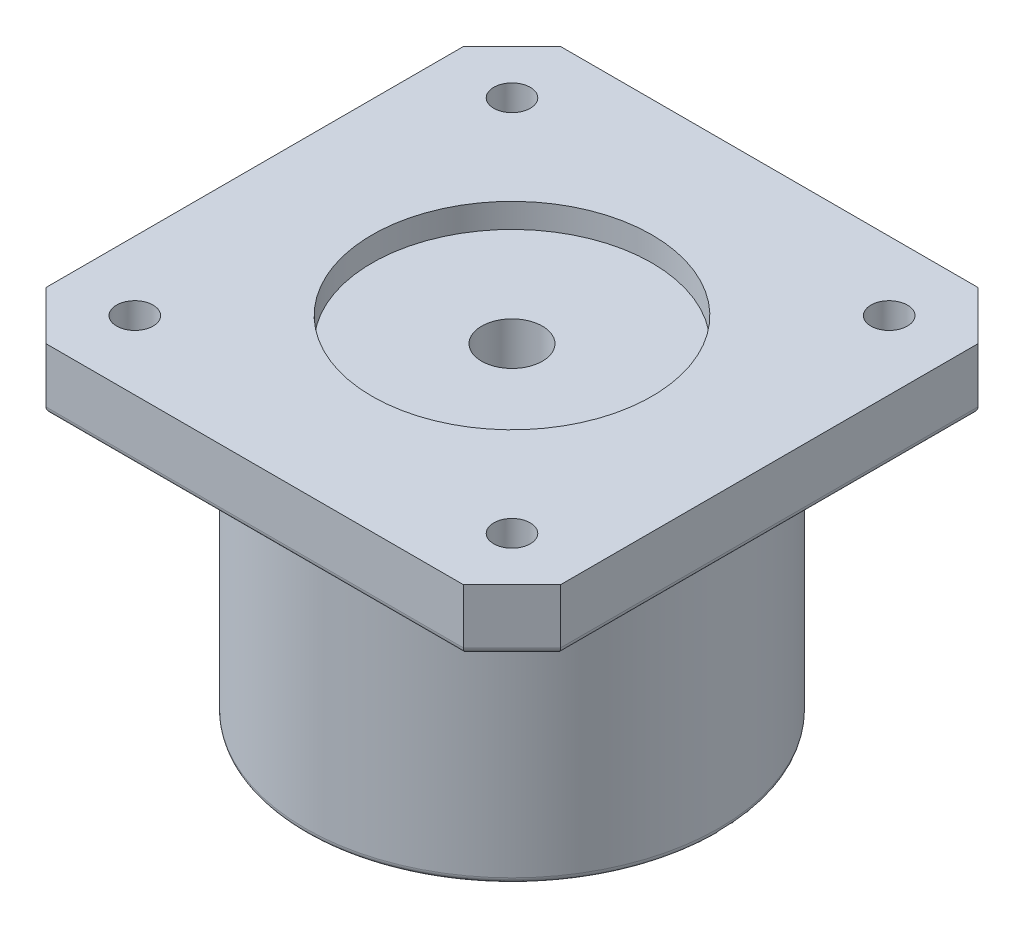
SolidWorks part; units mm, degrees
ref_plane "Front Plane" through (0, 0, 0) normal (0, 0, 1) x (1, 0, 0)
ref_plane "Top Plane" through (0, 0, 0) normal (0, 1, 0) x (1, 0, 0)
ref_plane "Right Plane" through (0, 0, 0) normal (1, 0, 0) x (0, 0, -1)
sketch "Sketch1" plane through (0, 0, 0) normal (0, 1, 0) x (1, 0, 0)
  line L1 (0, 0) -> (42.3, 0)
  line L2 (0, 0) -> (0, 42.3)
  line L3 (0, 42.3) -> (42.3, 42.3)
  line L4 (42.3, 0) -> (42.3, 42.3)
  dimension "D1" = 42.3
  dimension "D2" = 42.3
extrude "Boss-Extrude1" add sketch "Sketch1" along normal blind 5
sketch "Sketch2" plane through (0, 5, 0) normal (0, 1, 0) x (1, 0, 0)
  line L0 (0, 0) -> (0, 4)
  line L1 (0, 42.3) -> (0, 0) construction
  line L2 (0, 4) -> (4, 0)
  line L3 (0, 0) -> (42.3, 0) construction
  line L4 (4, 0) -> (0, 0)
  line L5 (38.3, 0) -> (42.3, 4)
  line L6 (42.3, 0) -> (42.3, 42.3) construction
  line L7 (42.3, 4) -> (42.3, 0)
  line L8 (42.3, 0) -> (38.3, 0)
  line L9 (38.3, 42.3) -> (42.3, 42.3)
  line L10 (42.3, 42.3) -> (0, 42.3) construction
  line L11 (42.3, 42.3) -> (42.3, 38.3)
  line L12 (42.3, 38.3) -> (38.3, 42.3)
  line L13 (0, 42.1095) -> (0, 42.3)
  line L14 (0, 42.3) -> (0, 38.3)
  line L15 (0, 38.3) -> (4, 42.3)
  line L16 (4, 42.3) -> (0, 42.3)
  line M4 (0, 42.3) -> (0, 0)
  line M5 (0, 0) -> (42.3, 0)
  line M6 (42.3, 0) -> (42.3, 42.3)
  line M7 (42.3, 42.3) -> (0, 42.3)
  dimension "D1" = 4
  dimension "D2" = 4
  dimension "D3" = 4
  dimension "D4" = 4
  dimension "D5" = 4
  dimension "D6" = 4
  dimension "D7" = 4
  dimension "D8" = 4
extrude "Cut-Extrude2" cut sketch "Sketch2" against normal blind 5 contours L2 M4 M5 | L15 M4 M7 | L12 M6 M7 | L5 M5 M6 region at (1.3333, 5, -1.3333) region at (1.3333, 5, -40.9667) region at (40.9667, 5, -1.3333) region at (40.9667, 5, -40.9667)
sketch "Sketch4" plane through (0, 5, 0) normal (0, 1, 0) x (1, 0, 0)
  circle A0 centre (21.15, 21.15) radius 11.5
  dimension "D1" = 23
extrude "Cut-Extrude3" cut sketch "Sketch4" against normal blind 2
sketch "Sketch5" plane through (0, 5, 0) normal (0, 1, 0) x (1, 0, 0)
  circle A0 centre (5.65, 36.65) radius 1.5
  circle A1 centre (36.65, 36.65) radius 1.5
  circle A2 centre (36.65, 5.65) radius 1.5
  circle A3 centre (5.65, 5.65) radius 1.5
  circle A4 centre (21.15, 21.15) radius 2.5
  point P2 (21.15, 21.15)
  dimension "D5" = 3
  dimension "D6" = 5
  dimension "D1" = 15.5
  dimension "D2" = 15.5
  dimension "D4" = 2
  dimension "D3" = 2
extrude "Cut-Extrude4" cut sketch "Sketch5" against normal blind 5
sketch "Sketch6" plane through (0, 0, 0) normal (0, -1, 0) x (1, 0, 0)
  circle A0 centre (21.15, -21.15) radius 17
  dimension "D1" = 34
extrude "Boss-Extrude2" add sketch "Sketch6" along normal blind 23.5
extrude "Cut-Extrude5" cut sketch "Sketch5<2>" against normal blind 28.5
sketch "Sketch5<2>" plane through (0, 5, 0) normal (0, 1, 0) x (1, 0, 0) same geometry as "Sketch5"
sketch "Sketch8" plane through (0, 0, 0) normal (0, -1, 0) x (-1, 0, 0)
  circle A0 centre (-5.65, 36.65) radius 2.8
  circle A1 centre (-36.6499, 36.5797) radius 2.8
  circle A2 centre (-36.5796, 5.5798) radius 2.8
  circle A3 centre (-5.5797, 5.6501) radius 2.8
  dimension "D1" = 5.6
  dimension "D2" = 2
extrude "Cut-Extrude6" cut sketch "Sketch8" against normal blind 2.37 contours A0 | A1 | A2 | A3
sketch "Sketch10" plane through (0, -23.5, 0) normal (0, -1, 0) x (-1, 0, 0)
  circle A0 centre (-21.7016, 8.15) radius 1.5
  circle A3 centre (-30.894, 11.9576) radius 1.5
  circle A4 centre (-34.7016, 21.15) radius 1.5
  circle A5 centre (-30.894, 30.3424) radius 1.5
  circle A6 centre (-21.7016, 34.15) radius 1.5
  circle A7 centre (-12.5093, 30.3424) radius 1.5
  circle A8 centre (-8.7016, 21.15) radius 1.5
  circle A9 centre (-12.5093, 11.9576) radius 1.5
  point P20 (-21.7016, 21.15)
  dimension "D1" = 3
  dimension "D2" = 13
  dimension "D3" = 8
extrude "Cut-Extrude7" cut sketch "Sketch10" against normal blind 10
fillet "Fillet1" radius 0.5 8 edges at (2, 0, -40.3) (0, 0, -21.15) (2, 0, -2) (21.15, 0, -42.3) (40.3, 0, -40.3) (42.3, 0, -21.15) (40.3, 0, -2) (21.15, 0, 0)
sketch "Sketch12" plane through (0, -23.5, 0) normal (0, -1, 0) x (-1, 0, 0)
  circle A0 centre (-8.7016, 21.15) radius 2.8
  circle A2 centre (-21.7016, 8.15) radius 2.8
  circle A3 centre (-34.7016, 21.15) radius 2.8
  circle A4 centre (-21.7016, 34.15) radius 2.8
  point P14 (-21.7016, 21.15)
  dimension "D1" = 5.6
  dimension "D2" = 4
extrude "Cut-Extrude8" cut sketch "Sketch12" against normal blind 2.37
fillet "Fillet2" radius 0.5 1 edges at (21.15, -23.5, -38.15)
sketch "Sketch13" plane through (0, -23.5, 0) normal (0, -1, 0) x (-1, 0, 0)
  circle A0 centre (-21.15, 21.15) radius 7.5
  dimension "D1" = 15
extrude "Cut-Extrude9" cut sketch "Sketch13" against normal blind 1
